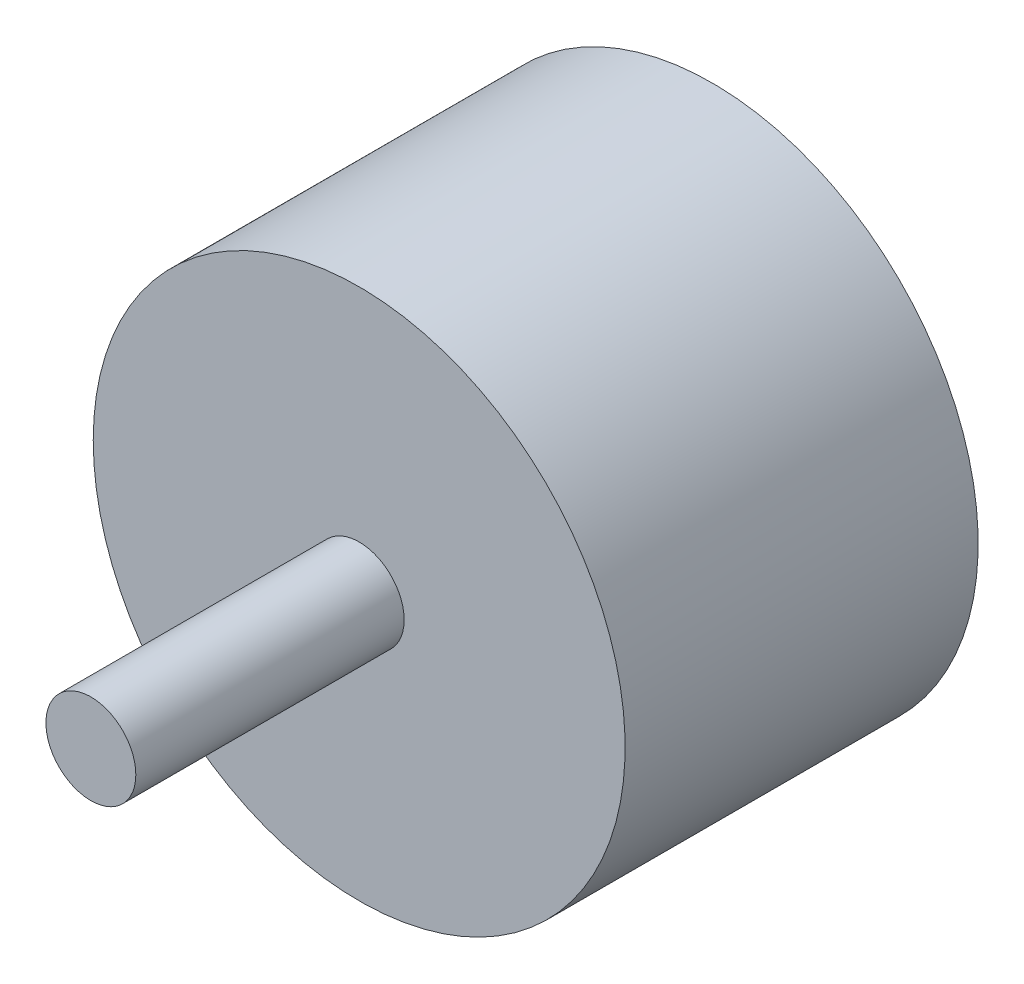
SolidWorks part; units mm, degrees
ref_plane "Front Plane" through (0, 0, 0) normal (0, 0, 1) x (1, 0, 0)
ref_plane "Top Plane" through (0, 0, 0) normal (0, 1, 0) x (1, 0, 0)
ref_plane "Right Plane" through (0, 0, 0) normal (1, 0, 0) x (0, 0, -1)
sketch "Sketch1" plane through (0, 0, 0) normal (0, 0, 1) x (1, 0, 0)
  circle A0 centre (0, 0) radius 14.351
  dimension "D1" = 28.702
extrude "Boss-Extrude1" add sketch "Sketch1" along normal blind 19.05
sketch "Sketch2" plane through (0, 0, 19.05) normal (0, 0, 1) x (1, 0, 0)
  circle A0 centre (0, 0) radius 2.4257
  dimension "D1" = 4.8514
extrude "Boss-Extrude2" add sketch "Sketch2" along normal blind 14.478
sketch "Sketch3" plane through (0, 0, 0) normal (0, 0, -1) x (-1, 0, 0)
  line L0 (0, 0) -> (0, 9.652) construction
  line L1 (0, 0) -> (9.652, 0) construction
  line L2 (0, 0) -> (-9.652, 0) construction
  line L3 (0, 0) -> (0, -9.652) construction
  circle A0 centre (0, 9.652) radius 1.2065
  circle A1 centre (9.652, 0) radius 1.2065
  circle A2 centre (0, -9.652) radius 1.2065
  circle A3 centre (-9.652, 0) radius 1.2065
  dimension "D2" = 2.413
  dimension "D1" = 9.652
extrude "Cut-Extrude1" cut sketch "Sketch3" against normal blind 5.08
